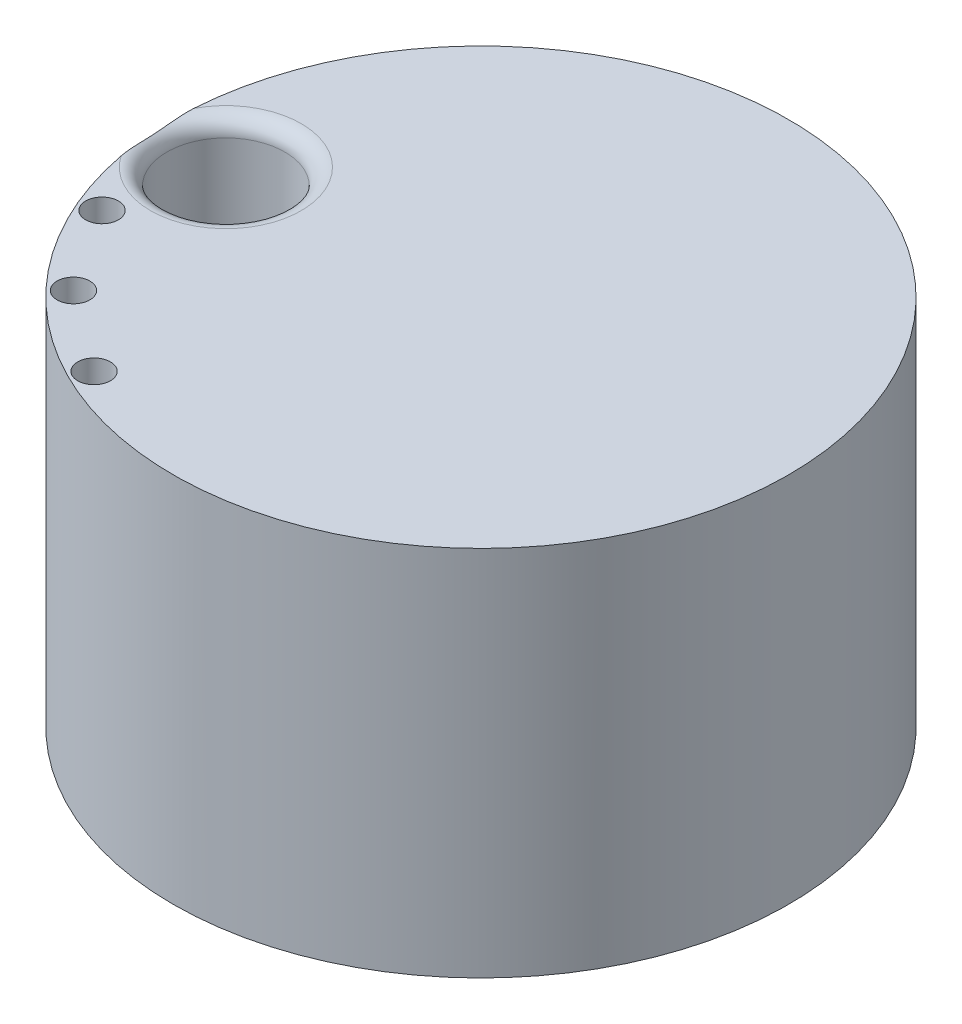
SolidWorks part; units mm, degrees
ref_plane "Front Plane" through (0, 0, 0) normal (0, 0, 1) x (1, 0, 0)
ref_plane "Top Plane" through (0, 0, 0) normal (0, 1, 0) x (1, 0, 0)
ref_plane "Right Plane" through (0, 0, 0) normal (1, 0, 0) x (0, 0, -1)
sketch "Sketch2" plane through (0, 0, 0) normal (0, 1, 0) x (1, 0, 0)
  circle A0 centre (0, 0) radius 47.6885
  dimension "D1" = 95.377
extrude "Boss-Extrude1" add sketch "Sketch2" along normal blind 57.658
sketch "Sketch4" plane through (0, 57.658, 0) normal (0, 1, 0) x (1, 0, 0)
  circle A1 centre (-26.162, 0) radius 3.175
  circle A2 centre (26.162, 0) radius 3.175
  circle A3 centre (0, 26.162) radius 3.175
  circle A4 centre (0, -26.162) radius 3.175
sketch "Sketch5" plane through (0, 57.658, 0) normal (0, 1, 0) x (1, 0, 0)
  line L0 (0, 0) -> (-32.4801, -30.672)
  line L1 (0, 0) -> (-41.0118, -17.7134)
  line L2 (0, 0) -> (-20.0308, -39.9311)
  line L3 (-46.3626, -2.3091) -> (-47.6326, -2.3091)
  circle A1 centre (-41.0118, -17.7134) radius 2.54
  circle A2 centre (0, 0) radius 44.6736
  circle A3 centre (-32.4801, -30.672) radius 2.54
  circle A4 centre (-20.0308, -39.9311) radius 2.54
  circle A9 centre (-37.2186, -2.3091) radius 9.144
  circle A10 centre (0, 0) radius 47.6885 construction
  point P7 (0, 0)
  point P8 (0, 0)
  dimension "D1" = 20
  dimension "D2" = 20
extrude "Cut-Extrude2" cut sketch "Sketch5" against normal through all contours A9 | A1 | A3 | A4
fillet "Fillet1" radius 2.54 1 edges at (-37.2186, 57.658, 11.4531)
